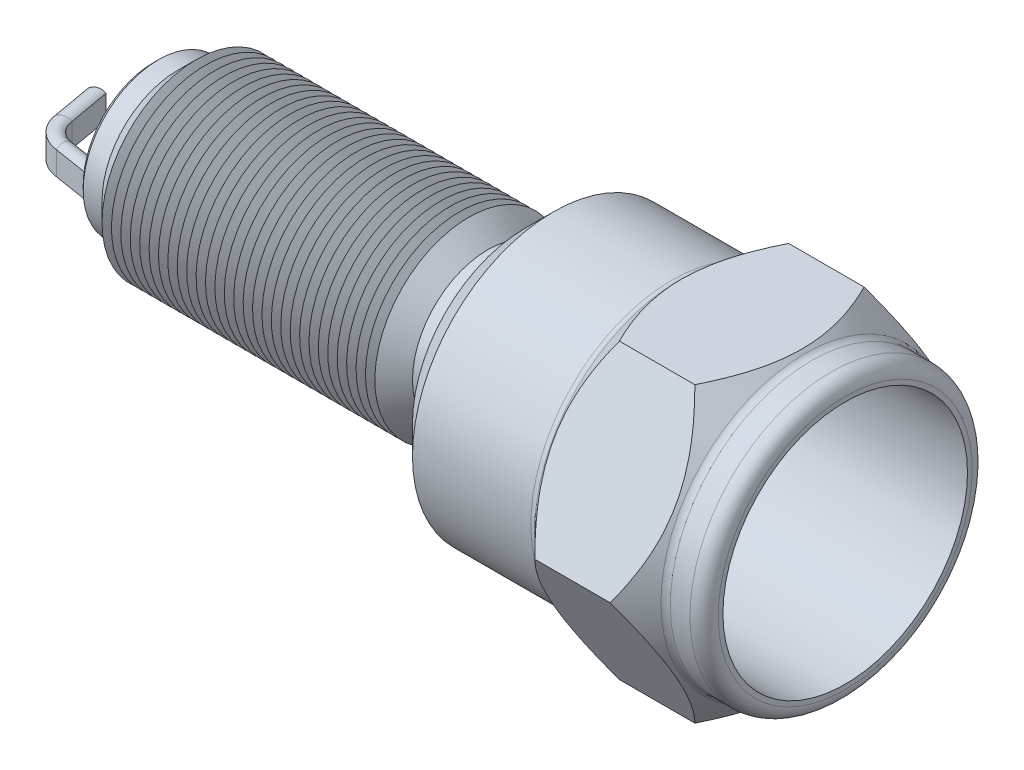
SolidWorks part; units mm, degrees
ref_plane "Front Plane" through (0, 0, 0) normal (0, 0, 1) x (1, 0, 0)
ref_plane "Top Plane" through (0, 0, 0) normal (0, 1, 0) x (1, 0, 0)
ref_plane "Right Plane" through (0, 0, 0) normal (1, 0, 0) x (0, 0, -1)
sketch "Sketch1" plane through (0, 0, 0) normal (0, 0, 1) x (1, 0, 0)
  line L0 (0, 0) -> (0, 4)
  line L1 (0, 4) -> (1.25, 4)
  line L2 (1.25, 4) -> (2.25, 5)
  line L3 (2.25, 5) -> (16.75, 5)
  line L4 (16.75, 5) -> (17.75, 4)
  line L5 (17.75, 4) -> (19.75, 4)
  line L6 (19.75, 4) -> (19.75, 7.5)
  line L7 (19.75, 7.5) -> (27.75, 7.5)
  line L8 (27.75, 7.5) -> (29.25, 9)
  line L9 (29.25, 9) -> (33.25, 9)
  line L10 (33.25, 9) -> (34.75, 7.5)
  line L11 (34.75, 7.5) -> (36.75, 7.5)
  line L12 (36.75, 7.5) -> (36.75, 0)
  line L13 (36.75, 0) -> (0, 0)
  dimension "D1" = 135
  dimension "D2" = 135
  dimension "D3" = 1.25
  dimension "D4" = 14.5
  dimension "D5" = 2
  dimension "D6" = 8
  dimension "D7" = 3.5
  dimension "D8" = 4
  dimension "D9" = 5
  dimension "D10" = 4
  dimension "D11" = 2
  dimension "D12" = 9
revolve "Revolve1" add sketch "Sketch1" angle 360 about L13
sketch "Sketch2" plane through (0, 0, 0) normal (0, 0, 1) x (1, 0, 0)
  line L0 (0, 0) -> (0, 3)
  line L1 (0, 4) -> (0, -4) construction
  line L2 (0, 3) -> (4.8, 3)
  line L3 (4.8, 3) -> (5.3, 2.5)
  line L4 (5.3, 2.5) -> (6.3, 2.5)
  line L5 (6.3, 2.5) -> (7.3, 3.5)
  line L6 (7.3, 3.5) -> (21.3, 3.5)
  line L7 (21.3, 3.5) -> (24.3, 6.5)
  line L8 (24.3, 6.5) -> (36.75, 6.5)
  line L9 (36.75, -7.5) -> (36.75, 7.5) construction
  line L10 (36.75, 6.5) -> (36.75, 0)
  line L11 (36.75, 0) -> (0, 0)
  dimension "D1" = 3
  dimension "D2" = 4.8
  dimension "D3" = 0.5
  dimension "D4" = 135
  dimension "D5" = 1
  dimension "D6" = 14
  dimension "D7" = 1
  dimension "D8" = 3
revolve "Cut-Revolve1" cut sketch "Sketch2" angle 360 about L11
sketch "Sketch4" plane through (19.75, 0, 0) normal (-1, 0, 0) x (0, 0, 1)
  line L1 (8.9951, 0) -> (4.4976, 7.79)
  line L2 (4.4976, 7.79) -> (-4.4976, 7.79)
  line L3 (-4.4976, 7.79) -> (-8.9951, 0)
  line L4 (-8.9951, 0) -> (-4.4976, -7.79)
  line L5 (-4.4976, -7.79) -> (4.4976, -7.79)
  line L6 (4.4976, -7.79) -> (8.9951, 0)
  circle A0 centre (0, 0) radius 7.79 construction
  point P1 (0, 7.79)
  dimension "D1" = 15.58
extrude "Cut-Extrude1" cut sketch "Sketch4" against normal through all flip side to cut
fillet "Fillet1" radius 0.75 1 edges at (36.75, 7.5, 0)
fillet "Fillet2" radius 0.5 3 edges at (27.75, 7.5, 0) (34.75, 7.5, 0) (19.75, 4, 0)
sketch "Sketch5" plane through (0, 0, 0) normal (0, 0, 1) x (1, 0, 0)
  line L1 (2.25, 5) -> (2.5, 4.567)
  line L2 (2.5, 4.567) -> (2.75, 5)
  line L3 (2.75, 5) -> (2.25, 5)
  line L4 (16.75, 5) -> (2.25, 5) construction
  circle A0 centre (2.5, 4.8557) radius 0.1443 construction
  dimension "D1" = 0.5
revolve "Cut-Revolve3" cut sketch "Sketch5" angle 360 about axis through (36.75, 0, 0) along (1, 0, 0)
pattern_linear "LPattern1" count 29 spacing 0.5 along (1, 0, 0) of "Cut-Revolve3"
sketch "Sketch7" plane through (0, 0, 0) normal (-1, 0, 0) x (0, 0, 1)
  line L0 (0, 0) -> (4, 0) construction
  line L2 (3, 0.625) -> (3.75, 0.625) construction
  line L3 (3, 0.625) -> (3, -0.625)
  line L4 (3, -0.625) -> (3.75, -0.625) construction
  line L5 (3.75, 0.625) -> (3.75, -0.625)
  line L6 (3, 0.625) -> (3.75, -0.625) construction
  line L7 (3, -0.625) -> (3.75, 0.625) construction
  circle A0 centre (0, 0) radius 4 construction
  arc A1 (3, 0.625) -> (3.75, 0.625) centre (3.375, 0.2505) cw
  circle A2 centre (0, 0) radius 3 construction
  arc A3 (3, -0.625) -> (3.75, -0.625) centre (3.375, -0.2505) ccw
  point P6 (3, 0)
  dimension "D3" = 0.53
  dimension "D1" = 1.25
  dimension "D2" = 0.75
sketch "Sketch9" plane through (0, 0, 0) normal (0, 1, 0) x (1, 0, 0)
  line L0 (0, -3.375) -> (-1.6932, -3.1068)
  line L1 (0, 0) -> (0, -4) construction
  line L2 (-2.9358, -1.8858) -> (-3.3231, 0.3106)
  line L3 (0, -3.375) -> (-23.0141, -3.375) construction
  line L4 (0, -3) -> (0, -3.75) construction
  arc A0 (-2.9358, -1.8858) -> (-1.6932, -3.1068) centre (-1.4586, -1.6253) ccw
  point P8 (0, -3.375)
  point P11 (-2.75, -2.9394)
  dimension "D5" = 1.5
  dimension "D1" = 9
  dimension "D2" = 2.75
  dimension "D3" = 109
  dimension "D4" = 3.25
sweep "Sweep2" add profiles "Sketch7" path "Sketch9"
chamfer "Chamfer1" distance 1.5 angle 45 1 edges at (19.75, 7.5, 0)
chamfer "Chamfer2" distance 0.25 angle 45 2 edges at (0, 4, 0) (0, 0, -3)
